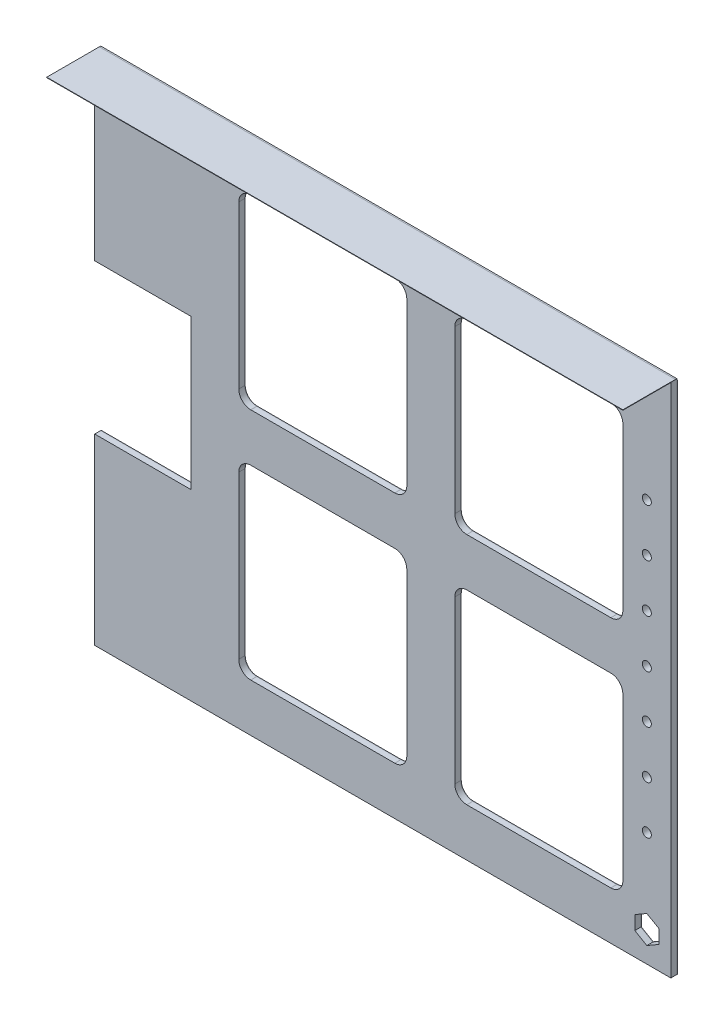
SolidWorks part; units mm, degrees
note: The reader was unsure of these and kept them because the rebuilt part matched: shared geometry of "Sketch1<2>"; flange length of "Edge-Flange1".
ref_plane "FRONT" through (0, 0, 0) normal (0, 0, 1) x (1, 0, 0)
ref_plane "TOP" through (0, 0, 0) normal (0, 1, 0) x (1, 0, 0)
ref_plane "RIGHT" through (0, 0, 0) normal (1, 0, 0) x (0, 0, -1)
sketch "Sketch1" plane through (0, 0, 0) normal (0, 0, 1) x (1, 0, 0)
  line L0 (177.8, 273.05) -> (177.8, 0) construction
  line L1 (0, 0) -> (304.8, 0)
  line L2 (0, 0) -> (0, 96.8375)
  line L3 (0, 273.05) -> (304.8, 273.05)
  line L4 (304.8, 0) -> (304.8, 273.05)
  line L5 (196.85, 247.65) -> (273.05, 247.65)
  line L6 (190.5, 241.3) -> (190.5, 155.575)
  line L7 (196.85, 149.225) -> (273.05, 149.225)
  line L8 (279.4, 241.3) -> (279.4, 155.575)
  line L9 (0, 136.525) -> (304.8, 136.525) construction
  line L10 (76.2, 241.3) -> (76.2, 155.575)
  line L11 (158.75, 149.225) -> (82.55, 149.225)
  line L12 (165.1, 241.3) -> (165.1, 155.575)
  line L13 (158.75, 247.65) -> (82.55, 247.65)
  line L14 (158.75, 25.4) -> (82.55, 25.4)
  line L15 (165.1, 31.75) -> (165.1, 117.475)
  line L16 (158.75, 123.825) -> (82.55, 123.825)
  line L17 (76.2, 31.75) -> (76.2, 117.475)
  line L18 (279.4, 31.75) -> (279.4, 117.475)
  line L19 (196.85, 123.825) -> (273.05, 123.825)
  line L20 (190.5, 31.75) -> (190.5, 117.475)
  line L21 (196.85, 25.4) -> (273.05, 25.4)
  line L22 (0, 176.2125) -> (0, 273.05)
  line L23 (0, 176.2125) -> (50.8, 176.2125)
  line L24 (292.1, 15.8667) -> (292.1, 23.1991) construction
  line L25 (0, 96.8375) -> (50.8, 96.8375)
  line L26 (50.8, 176.2125) -> (50.8, 96.8375)
  line L27 (298.45, 12.2006) -> (298.45, 19.5329)
  line L28 (298.45, 19.5329) -> (292.1, 23.1991)
  line L29 (292.1, 23.1991) -> (285.75, 19.5329)
  line L30 (285.75, 19.5329) -> (285.75, 12.2006)
  line L31 (285.75, 12.2006) -> (292.1, 8.5344)
  line L32 (292.1, 8.5344) -> (298.45, 12.2006)
  arc A0 (279.4, 241.3) -> (273.05, 247.65) centre (273.05, 241.3) ccw
  arc A1 (279.4, 155.575) -> (273.05, 149.225) centre (273.05, 155.575) cw
  arc A2 (196.85, 149.225) -> (190.5, 155.575) centre (196.85, 155.575) cw
  arc A3 (196.85, 247.65) -> (190.5, 241.3) centre (196.85, 241.3) ccw
  arc A4 (158.75, 247.65) -> (165.1, 241.3) centre (158.75, 241.3) cw
  arc A5 (158.75, 149.225) -> (165.1, 155.575) centre (158.75, 155.575) ccw
  arc A6 (76.2, 155.575) -> (82.55, 149.225) centre (82.55, 155.575) ccw
  arc A7 (76.2, 241.3) -> (82.55, 247.65) centre (82.55, 241.3) cw
  arc A8 (76.2, 31.75) -> (82.55, 25.4) centre (82.55, 31.75) ccw
  arc A9 (76.2, 117.475) -> (82.55, 123.825) centre (82.55, 117.475) cw
  arc A10 (158.75, 123.825) -> (165.1, 117.475) centre (158.75, 117.475) cw
  arc A11 (158.75, 25.4) -> (165.1, 31.75) centre (158.75, 31.75) ccw
  arc A12 (196.85, 25.4) -> (190.5, 31.75) centre (196.85, 31.75) cw
  arc A13 (196.85, 123.825) -> (190.5, 117.475) centre (196.85, 117.475) ccw
  arc A14 (279.4, 117.475) -> (273.05, 123.825) centre (273.05, 117.475) ccw
  arc A15 (279.4, 31.75) -> (273.05, 25.4) centre (273.05, 31.75) cw
  circle A16 centre (292.1, 15.8667) radius 6.35 construction
  circle A17 centre (292.1, 60.325) radius 2.3876
  circle A18 centre (292.1, 85.725) radius 2.3876
  circle A19 centre (292.1, 111.125) radius 2.3876
  circle A20 centre (292.1, 136.525) radius 2.3876
  circle A21 centre (292.1, 161.925) radius 2.3876
  circle A22 centre (292.1, 187.325) radius 2.3876
  circle A23 centre (292.1, 212.725) radius 2.3876
  point P61 (50.8, 136.525)
  dimension "D5" = 6.35
  dimension "D6" = 6.35
  dimension "D14" = 12.7
  dimension "D16" = 4.7752
  dimension "D1" = 273.05
  dimension "D2" = 304.8
  dimension "D3" = 25.4
  dimension "D4" = 25.4
  dimension "D7" = 88.9
  dimension "D8" = 98.425
  dimension "D9" = 12.7
  dimension "D10" = 12.7
  dimension "D11" = 50.8
  dimension "D12" = 79.375
  dimension "D13" = 6.35
  dimension "D15" = 8.5344
  dimension "D17" = 60.325
  dimension "D18" = 12.7
  dimension "D19" = 7
extrude "Boss-Extrude1" add sketch "Sketch1" along normal blind 3.175
base flange "Base-Flange1" sketch "Sketch1<2>" thickness 0.2286 reverse thickness direction no parameters "D1"=0.7366
sketch "Sketch1<2>" plane through (0, 0, 0) normal (0, 0, 1) x (1, 0, 0) same geometry as "Sketch1"
edge flange "Edge-Flange1" sketch "Sketch10" flange angle 90 flange length 28.8036 flange position material inside bend radius 0.7366 thickness 0.2286 relief rectangular parameters "D6"=10
sketch "Sketch10" plane through (0, 273.05, 0) normal (0, -1, 0) x (1, 0, 0)
  line L1 (304.8, 0) -> (0, 0) construction
  line L2 (0, 0) -> (0, 28.575)
  line L3 (0, 28.575) -> (304.8, 28.575)
  line L4 (304.8, 28.575) -> (304.8, 0)
  line L5 (304.8, 0) -> (0, 0)
  dimension "D1" = 28.575
bend "EdgeBend1" bend radius 0.7366 bend angle 90 parameters "D5"=1
sketch "Bend-Lines1" [suppressed] plane through (0, 0, 0) normal (0, 1, 0) x (1, 0, 0)
sketch "Bounding-Box1" [suppressed] plane through (0, 0, 0) normal (0, 1, 0) x (1, 0, 0)
sheet metal parameters "Sheet-Metal6" thickness 0.2286 parameters "D1"=0.7366
flat pattern "Flat-Pattern6" [suppressed]
sketch "Bend-Lines2" plane through (0, 0, 0) normal (0, 1, 0) x (1, 0, 0)
sketch3d "Bounding-Box2" [suppressed]
  line L0 (0, 0, 0) -> (-304.8, 0, 0) construction
  line L1 (0, 273.05, 0) -> (-304.8, 273.05, 0) construction
  line L2 (0, 0, 0) -> (0, 273.05, 0) construction
  line L3 (-304.8, 0, 0) -> (-304.8, 273.05, 0) construction
sheet metal parameters "Sheet-Metal7" thickness 0.2286 parameters "D1"=0.7366
flat pattern "Flat-Pattern6"
sketch "Bend-Lines2" plane through (0, 0, 0) normal (0, 0, 1) x (1, 0, 0)
  line L0 (304.8, 272.7226) -> (0, 272.7226) construction
  line L1 (304.8, 272.7226) -> (0, 272.7226) construction
sketch3d "Bounding-Box2" [suppressed]
  line L0 (0, 0, 0) -> (304.8, 0, 0) construction
  line L1 (0, 301.1987, 0) -> (304.8, 301.1987, 0) construction
  line L2 (0, 0, 0) -> (0, 301.1987, 0) construction
  line L3 (304.8, 0, 0) -> (304.8, 301.1987, 0) construction
bend of the flat pattern "Flatten-<EdgeBend1>1"
